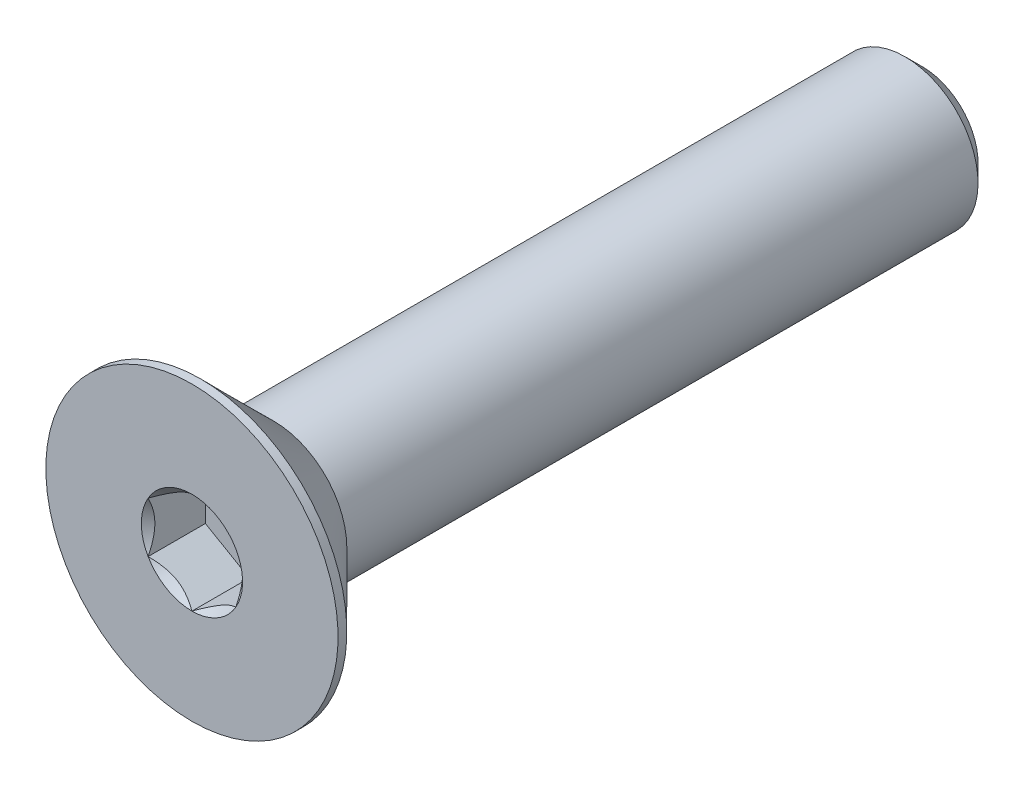
SolidWorks part; units mm, degrees
ref_plane "Front" through (0, 0, 0) normal (0, 0, 1) x (1, 0, 0)
ref_plane "Top" through (0, 0, 0) normal (0, 1, 0) x (1, 0, 0)
ref_plane "Right" through (0, 0, 0) normal (1, 0, 0) x (0, 0, -1)
sketch "Sketch1" plane through (0, 0, 0) normal (1, 0, 0) x (0, 0, -1)
  line L0 (0, 5) -> (0.3, 5) construction
  line L1 (0.3, 5) -> (2.8, 2.5) construction
  line L2 (0, 2.5) -> (25, 2.5)
  line L3 (25, 2.5) -> (25, 0)
  line L4 (25, 0) -> (0, 0)
  line L5 (0, 0) -> (0, 5) construction
  line L6 (0, 5) -> (0, -5) construction
  line L7 (25, 2.5) -> (25, -2.5) construction
  line L8 (0, -5) -> (0.3, -5) construction
  line L9 (0.3, -5) -> (2.8, -2.5) construction
  line L11 (0, 2.5) -> (0, 0)
  line L12 (2.8, 2.5) -> (2.8, 0) construction
revolve "Revolve1" add sketch "Sketch1" angle 360 mid plane about L4
sketch "Sketch3" plane through (0, 0, -25) normal (0, 0, -1) x (-1, 0, 0)
  circle A0 centre (0, 0) radius 2.5
curve "Helix/Spiral1" pitch 0.8 height 25 turns 31.25
sketch "Sketch2" plane through (0, 0, 0) normal (1, 0, 0) x (0, 0, -1)
  line L0 (25, 2.5) -> (25.7, 2.5)
  line L1 (25.7, 2.5) -> (25.4, 1.9804)
  line L2 (25.4, 1.9804) -> (25.3, 1.9804)
  line L3 (25.3, 1.9804) -> (25, 2.5)
  line L4 (25.15, 2.2402) -> (25.55, 2.2402) construction
  dimension "D1" = 60
  dimension "D2" = 0.1
  dimension "D3" = 0.4
chamfer "Chamfer1" distance 0.6 angle 45 1 edges at (0, 2.5, -25)
sweep "Cut-Sweep1" [suppressed] cut profiles "Sketch2" path "Helix/Spiral1"
sketch "Sketch7" plane through (0, 0, 0) normal (1, 0, 0) x (0, 0, -1)
  line L0 (0, 5) -> (0.3, 5) construction
  line L1 (0.3, 5) -> (2.8, 2.5) construction
  line L2 (0, 5) -> (0.3, 5)
  line L3 (0.3, 5) -> (2.8, 2.5)
  line L4 (2.8, 2.5) -> (2.8, 0) construction
  line L5 (2.8, 2.5) -> (2.8, 0)
  line L7 (0, 0) -> (0, 5) construction
  line L8 (0, 0) -> (0, 5)
  line L9 (0, 0) -> (2.8, 0)
  line L10 (55, 0) -> (-55, 0) construction
revolve "Revolve2" add sketch "Sketch7" angle 360 mid plane about L9
ref_plane "Plane1" through (0, 0, -2.8) normal (0, 0, 1) x (1, 0, 0)
sketch "Sketch8" plane through (0, 0, -2.8) normal (0, 0, 1) x (1, 0, 0)
  circle A0 centre (0, 0) radius 2.5
extrude "Boss-Extrude1" add sketch "Sketch8" against normal through all draft 45
sketch "Sketch5" plane through (0, 0, 0) normal (0, 0, 1) x (1, 0, 0)
  line L1 (1.5, -0.866) -> (1.5, 0.866)
  line L2 (1.5, 0.866) -> (0, 1.7321)
  line L3 (0, 1.7321) -> (-1.5, 0.866)
  line L4 (-1.5, 0.866) -> (-1.5, -0.866)
  line L5 (-1.5, -0.866) -> (0, -1.7321)
  line L6 (0, -1.7321) -> (1.5, -0.866)
  circle A0 centre (0, 0) radius 1.5 construction
  dimension "Hex" = 3
extrude "Cut-Extrude2" cut sketch "Sketch5" against normal blind 1.96
sketch "Sketch6" plane through (0, 0, 0) normal (0, 0, 1) x (1, 0, 0)
  circle A0 centre (0, 0) radius 1.7321
extrude "Cut-Extrude3" cut sketch "Sketch6" against normal blind 1.96 draft 45
sketch "Sketch9" [suppressed] plane through (0, 0, -5.5) normal (0, 0, 1) x (1, 0, 0)
  circle A1 centre (0, 0) radius 5
  circle A2 centre (0, 0) radius 5
  point P0 (0, 5)
  dimension "D1" = 0
extrude "Boss-Extrude2" [suppressed] add sketch "Sketch9" against normal offset from surface (18.5 mm away) 26 up to face at (0, 1.9, -25)
fillet "Fillet1" [suppressed] radius 0.5
sketch "Sketch10" plane through (0, 0, 0) normal (1, 0, 0) x (0, 0, -1)
  line L0 (25, 2.5) -> (25, -2.5) construction
  point P0 (23.8, -2.5)
  dimension "D1" = 1.2
equation "\"D3@Helix/Spiral1\" = \"Lg@Sketch1\""
equation "\"D2@Sketch2\" = \"D4@Helix/Spiral1\" * .125"
equation "\"D3@Sketch2\" = \"D4@Helix/Spiral1\" * .5"
equation "\"D1@Chamfer1\" = \"D4@Helix/Spiral1\" * .75"
equation "\"D1@Cut-Extrude2\" = \"Head Ht@Sketch1\" * .7"
equation "\"D1@Sketch10\" = \"D4@Helix/Spiral1\" * 1.5"
equation "\"D1@Cut-Extrude3\" = \"D1@Cut-Extrude2\""
equation "\"D1@Fillet1\" = \"Dia@Sketch1\" * .1"
